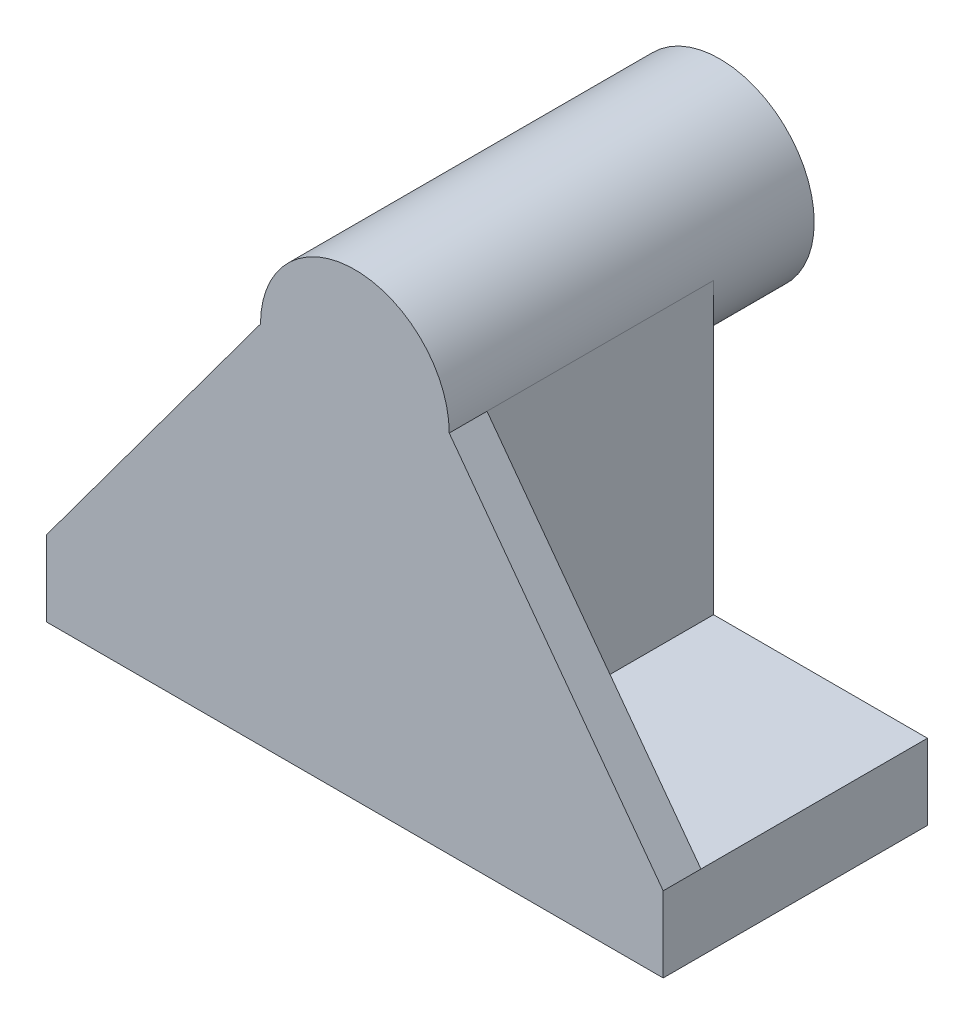
SolidWorks part; units mm, degrees
ref_plane "Front Plane" through (0, 0, 0) normal (0, 0, 1) x (1, 0, 0)
ref_plane "Top Plane" through (0, 0, 0) normal (0, 1, 0) x (1, 0, 0)
ref_plane "Right Plane" through (0, 0, 0) normal (1, 0, 0) x (0, 0, -1)
sketch "Sketch1" plane through (0, 0, 0) normal (0, 0, 1) x (1, 0, 0)
  line L0 (-7.5, 0) -> (-7.5, -29)
  line L1 (-7.5, -29) -> (24.5, -29)
  line L2 (24.5, -29) -> (24.5, -23)
  line L3 (24.5, -23) -> (7.5, -23)
  line L4 (7.5, -23) -> (7.5, 0)
  arc A0 (7.5, 0) -> (-7.5, 0) centre (0, 0) ccw
  dimension "D1" = 15
  dimension "D2" = 6
  dimension "D3" = 29
  dimension "D4" = 17
extrude "Main Body" add sketch "Sketch1" along normal blind 10.5 and the other way blind 10.5
sketch "Sketch2" plane through (0, 0, 10.5) normal (0, 0, 1) x (1, 0, 0)
  line L0 (7.5, 0) -> (24.5, -23)
rib "Rib1" sketch "Sketch2" sketch "Sketch2" thickness 3 extrusion direction parallel to sketch draft on no parameters "D1"=3
sketch "Sketch3" plane through (0, 0, -10.5) normal (0, 0, 1) x (1, 0, 0)
  arc A1 (7.5, 0) -> (-7.5, 0) centre (0, 0) ccw construction
  arc A2 (7.5, 0) -> (-7.5, 0) centre (0, 0) ccw construction
  circle A3 centre (0, 0) radius 7.5
extrude "Shaft" add sketch "Sketch3" against normal blind 8
mirror "Mirror2" about plane through (0, 0, 0) normal (1, 0, 0) of "Rib1", "Main Body"
